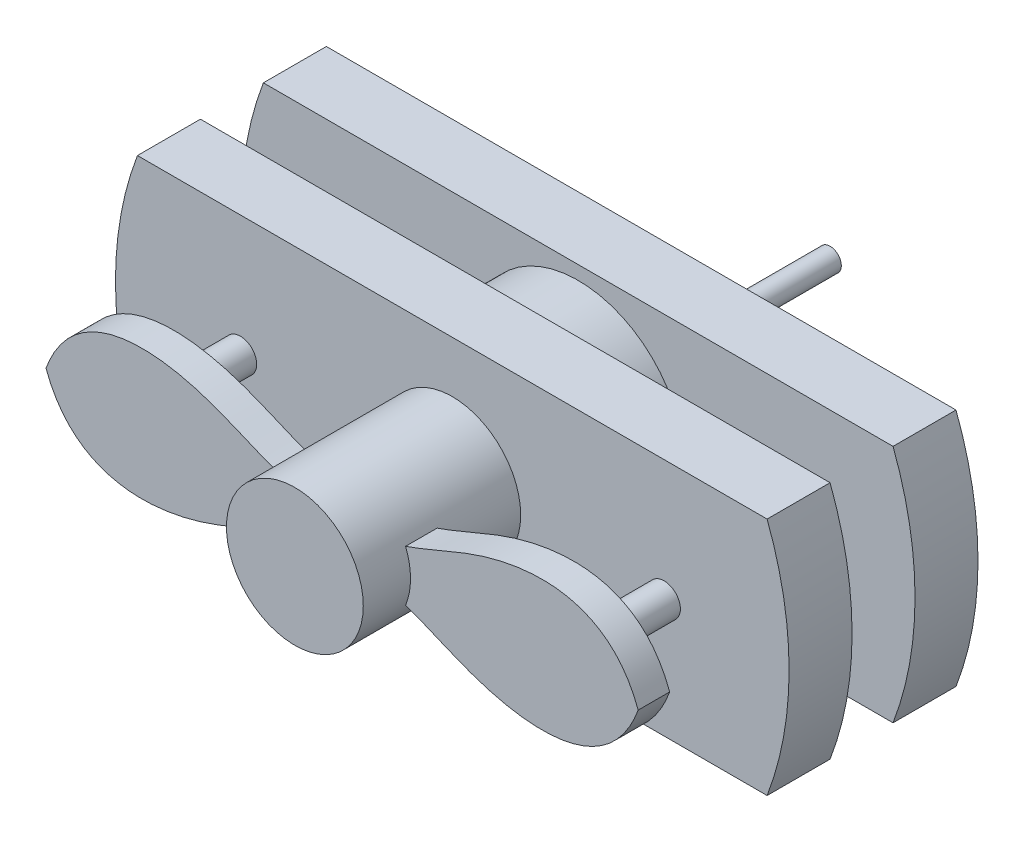
SolidWorks part; units mm, degrees
ref_plane "Front Plane" through (0, 0, 0) normal (0, 0, 1) x (1, 0, 0)
ref_plane "Top Plane" through (0, 0, 0) normal (0, 1, 0) x (1, 0, 0)
ref_plane "Right Plane" through (0, 0, 0) normal (1, 0, 0) x (0, 0, -1)
sketch "Sketch1" plane through (0, 0, 0) normal (0, 0, 1) x (1, 0, 0)
  line L0 (12.7, 16.2338) -> (12.7, -8.0341) construction
  line L1 (0, 0) -> (25.4, 0)
  line L3 (0, 9.6589) -> (25.4, 9.6589)
  arc A0 (0, 9.6589) -> (0, 0) centre (12.7, 4.8295) ccw
  arc A1 (25.4, 9.6589) -> (25.4, 0) centre (12.7, 4.8295) cw
  dimension "D1" = 25.4
extrude "Boss-Extrude1" add sketch "Sketch1" along normal blind 2.54
sketch "Sketch2" plane through (0, 0, 2.54) normal (0, 0, 1) x (1, 0, 0)
  line L0 (12.7, 11.2695) -> (12.7, -2.374) construction
  line L1 (-1.8056, 4.8295) -> (29.3481, 4.8295) construction
  circle A0 centre (12.7, 4.8295) radius 4.2772
extrude "Boss-Extrude2" add sketch "Sketch2" along normal blind 2.54
sketch "Sketch4" plane through (0, 0, 2.54) normal (0, 0, 1) x (1, 0, 0)
  line L0 (25.4, 0) -> (0, 0)
  line L1 (25.4, 9.6589) -> (0, 9.6589)
  arc A0 (0, 0) -> (0, 9.6589) centre (12.7, 4.8295) cw
  arc A1 (25.4, 0) -> (25.4, 9.6589) centre (12.7, 4.8295) ccw
extrude "Boss-Extrude3" add sketch "Sketch4" along normal blind 2.54 from surface starting at face at (16.9772, 4.8295, 5.08)
sketch "Sketch5" plane through (0, 0, 7.62) normal (0, 0, 1) x (1, 0, 0)
  line L0 (12.7, -1.8569) -> (12.7, 10.6785) construction
  line L1 (27.6735, 4.8295) -> (-3.825, 4.8295) construction
  spline S0 degree 3 poles (12.7, 4.2015) (14.8107, 4.3187) (18.3387, 1.8792) (23.5399, 1.8287) (24.6443, 4.8295) knots 0 0 0 0 0.434444 1 1 1 1
  spline S1 degree 3 poles (12.7, 5.4575) (14.8107, 5.3403) (18.3387, 7.7798) (23.5399, 7.8302) (24.6443, 4.8295) knots 0 0 0 0 0.434444 1 1 1 1
  spline S2 degree 3 poles (12.7, 5.4575) (10.5893, 5.3403) (7.0613, 7.7798) (1.8601, 7.8302) (0.7557, 4.8295) knots 0 0 0 0 0.434444 1 1 1 1
  spline S3 degree 3 poles (12.7, 4.2015) (10.5893, 4.3187) (7.0613, 1.8792) (1.8601, 1.8287) (0.7557, 4.8295) knots 0 0 0 0 0.434444 1 1 1 1
extrude "Boss-Extrude4" add sketch "Sketch5" along normal blind 1.27 from offset 3.175 separate body
sketch "Sketch6" plane through (0, 0, 12.065) normal (0, 0, 1) x (1, 0, 0)
  line L0 (12.7, -0.6994) -> (12.7, 11.4173) construction
  circle A0 centre (21.2457, 4.7679) radius 0.6558
  circle A1 centre (4.1543, 4.7679) radius 0.6558
extrude "Boss-Extrude5" add sketch "Sketch6" against normal up to surface (9.525 mm away) up to face at (16.9772, 4.8295, 2.54)
sketch "Sketch7" plane through (0, 0, 7.62) normal (0, 0, 1) x (1, 0, 0)
  line L0 (12.7, -1.2412) -> (12.7, 11.3434) construction
  line L1 (-1.8302, 4.8295) -> (27.969, 4.8295) construction
  circle A0 centre (12.7, 4.8295) radius 2.7596
extrude "Boss-Extrude6" add sketch "Sketch7" along normal blind 6.35
sketch "Sketch8" plane through (0, 0, 0) normal (0, 0, -1) x (-1, 0, 0)
  line L0 (-12.7, -1.1) -> (-12.7, 10.6357) construction
  line L1 (1.9943, 4.8295) -> (-27.5422, 4.8295) construction
  circle A0 centre (-12.7, 4.7678) radius 0.4533
extrude "Boss-Extrude7" add sketch "Sketch8" along normal blind 7.62
